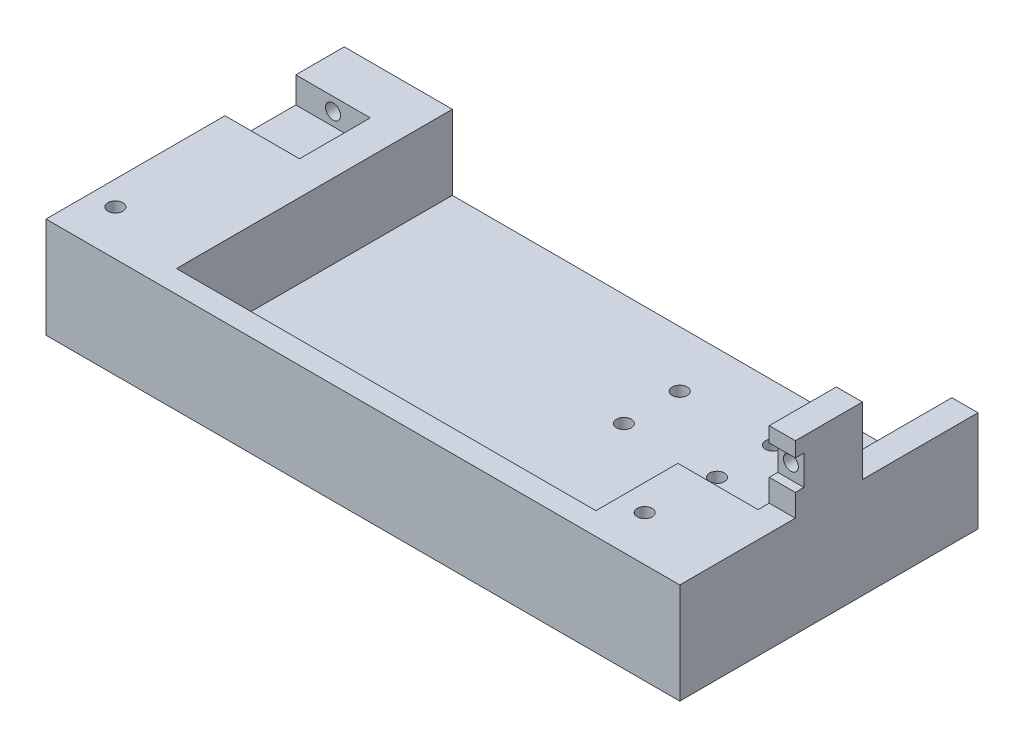
SolidWorks part; units mm, degrees
ref_plane "Front Plane" through (0, 0, 0) normal (0, 0, 1) x (1, 0, 0)
ref_plane "Top Plane" through (0, 0, 0) normal (0, 1, 0) x (1, 0, 0)
ref_plane "Right Plane" through (0, 0, 0) normal (1, 0, 0) x (0, 0, -1)
sketch "Sketch1" plane through (0, 0, 0) normal (0, 1, 0) x (1, 0, 0)
  line L1 (-79.8297, 39.708) -> (90.1703, 39.708)
  line L2 (-79.8297, 39.708) -> (-79.8297, -40.292)
  line L3 (-79.8297, -40.292) -> (90.1703, -40.292)
  line L4 (90.1703, 39.708) -> (90.1703, -40.292)
  dimension "D1" = 170
  dimension "D2" = 80
extrude "Boss-Extrude1" add sketch "Sketch1" along normal blind 7
sketch "Sketch2" plane through (0, 7, 0) normal (0, 1, 0) x (1, 0, 0)
  line L0 (-79.8297, 39.708) -> (-79.8297, -40.292) construction
  line L1 (-79.8297, -40.292) -> (90.1703, -40.292) construction
  line L2 (-79.8297, 8.708) -> (-72.8297, 8.708)
  line L3 (-79.8297, 8.708) -> (-79.8297, -9.292)
  line L4 (-79.8297, -9.292) -> (-72.8297, -9.292)
  line L5 (-72.8297, 8.708) -> (-72.8297, -9.292)
  line L6 (90.1703, 39.708) -> (-79.8297, 39.708) construction
  dimension "D1" = 7
  dimension "D2" = 18
  dimension "D3" = 31
  dimension "D4" = 31
extrude "Boss-Extrude2" add sketch "Sketch2" along normal blind 18
sketch "Sketch3" plane through (0, 0, -8.708) normal (0, 0, -1) x (-1, 0, 0)
  line L0 (79.8297, 25) -> (79.8297, 7) construction
  line L1 (72.8297, 7) -> (79.8297, 7) construction
  circle A0 centre (76.3297, 17) radius 2
  dimension "D1" = 3.5
  dimension "D2" = 10
extrude "Cut-Extrude1" cut sketch "Sketch3" against normal blind 20
sketch "Sketch4" plane through (0, 0, 9.292) normal (0, 0, 1) x (1, 0, 0)
  line L0 (-79.8297, 25) -> (-79.8297, 7) construction
  line L1 (-79.8297, 21) -> (-72.8297, 21)
  line L2 (-79.8297, 21) -> (-79.8297, 13)
  line L3 (-79.8297, 13) -> (-72.8297, 13)
  line L4 (-72.8297, 21) -> (-72.8297, 13)
  line L5 (-72.8297, 25) -> (-72.8297, 7) construction
  line L6 (-79.8297, 7) -> (90.1703, 7) construction
  dimension "D1" = 8
  dimension "D2" = 6
extrude "Cut-Extrude2" cut sketch "Sketch4" against normal blind 2.3
sketch "Sketch6" plane through (0, 7, 0) normal (0, 1, 0) x (1, 0, 0)
  line L1 (90.1703, -40.292) -> (90.1703, 39.708) construction
  line L2 (90.1703, 39.708) -> (-79.8297, 39.708) construction
  line L3 (70.1703, 7.708) -> (90.1703, 7.708)
  line L4 (70.1703, 7.708) -> (70.1703, 26.708)
  line L5 (70.1703, 26.708) -> (90.1703, 26.708)
  line L6 (90.1703, 7.708) -> (90.1703, 26.708)
  dimension "D3" = 20
  dimension "D4" = 13
  dimension "D5" = 19
extrude "Cut-Extrude4" cut sketch "Sketch6" against normal blind 11
sketch "Sketch7" plane through (0, 0, -26.708) normal (0, 0, 1) x (1, 0, 0)
  line L0 (90.1703, 0) -> (90.1703, 7) construction
  line L1 (90.1703, 7) -> (70.1703, 7) construction
  circle A0 centre (80.1703, 3.5) radius 2
  dimension "D1" = 10
  dimension "D2" = 3.5
extrude "Cut-Extrude5" cut sketch "Sketch7" against normal blind 25
extrude "Cut-Extrude6" cut sketch "Sketch7<2>" along normal blind 25
sketch "Sketch7<2>" plane through (0, 0, -26.708) normal (0, 0, 1) x (1, 0, 0) same geometry as "Sketch7"
sketch "Sketch8" plane through (0, 0, 0) normal (0, -1, 0) x (1, 0, 0)
  line L1 (-79.8297, 40.292) -> (90.1703, 40.292)
  line L2 (-79.8297, 40.292) -> (-79.8297, -39.708)
  line L3 (-79.8297, -39.708) -> (90.1703, -39.708)
  line L4 (90.1703, 40.292) -> (90.1703, -39.708)
extrude "Boss-Extrude3" add sketch "Sketch8" along normal blind 20
sketch "Sketch9" plane through (0, 7, 0) normal (0, 1, 0) x (1, 0, 0)
  line L0 (-79.8297, -40.292) -> (90.1703, -40.292) construction
  line L1 (-72.8297, -40.292) -> (61.1703, -40.292)
  line L2 (-72.8297, -40.292) -> (-72.8297, 39.708)
  line L3 (-72.8297, 39.708) -> (61.1703, 39.708)
  line L4 (61.1703, -40.292) -> (61.1703, 39.708)
  line L5 (90.1703, 39.708) -> (-79.8297, 39.708) construction
  line L6 (-72.8297, -9.292) -> (-72.8297, 8.708) construction
  line L7 (70.1703, 26.708) -> (70.1703, 7.708) construction
  dimension "D1" = 0
  dimension "D2" = 9
extrude "Cut-Extrude7" cut sketch "Sketch9" against normal blind 20
sketch "Sketch12" plane through (0, -13, 0) normal (0, 1, 0) x (1, 0, 0)
  line L0 (-72.8297, -9.292) -> (-72.8297, -40.292) construction
  line L1 (-72.8297, -12.292) -> (61.1703, -12.292)
  line L2 (-72.8297, -12.292) -> (-72.8297, -40.292)
  line L3 (-72.8297, -40.292) -> (61.1703, -40.292)
  line L4 (61.1703, -12.292) -> (61.1703, -40.292)
  dimension "D1" = 28
extrude "Boss-Extrude4" add sketch "Sketch12" along normal blind 20
sketch "Sketch10" plane through (0, -20, 0) normal (0, -1, 0) x (1, 0, 0)
  line L1 (90.1703, 40.292) -> (-79.8297, 40.292) construction
  line L2 (-79.8297, 40.292) -> (-79.8297, -39.708) construction
  circle A0 centre (83.6703, 28.192) radius 2
  circle A2 centre (-58.3297, 28.192) radius 2
  dimension "D1" = 21.5
  dimension "D2" = 142
  dimension "D3" = 12.1
  dimension "D4" = 12.1
extrude "Cut-Extrude9" cut sketch "Sketch10" against normal through all both and the other way through all
sketch "Sketch13" plane through (0, 7, 0) normal (0, 1, 0) x (1, 0, 0)
  line L0 (61.1703, -12.292) -> (-72.8297, -12.292) construction
  line L1 (-51.3297, -12.292) -> (61.1703, -12.292)
  line L2 (-51.3297, -12.292) -> (-51.3297, -34.292)
  line L3 (-51.3297, -34.292) -> (61.1703, -34.292)
  line L4 (61.1703, -12.292) -> (61.1703, -34.292)
  line L5 (61.1703, -12.292) -> (61.1703, 39.708) construction
  line L6 (-79.8297, -40.292) -> (90.1703, -40.292) construction
  circle A0 centre (-58.3297, -28.192) radius 2 construction
  dimension "D1" = 0
  dimension "D2" = 6
  dimension "D3" = 7
extrude "Cut-Extrude10" cut sketch "Sketch13" against normal blind 20
sketch "Sketch14" plane through (0, -13, 0) normal (0, 1, 0) x (1, 0, 0)
  line L0 (-79.8297, -40.292) -> (-79.8297, 39.708) construction
  line L1 (-79.8297, 39.708) -> (90.1703, 39.708) construction
  circle A0 centre (-39.8297, 24.708) radius 2
  circle A1 centre (-39.8297, 9.708) radius 2
  circle A2 centre (-14.8297, 9.708) radius 2
  circle A3 centre (-14.8297, 24.708) radius 2
  dimension "D1" = 40
  dimension "D3" = 25
  dimension "D2" = 15
  dimension "D4" = 25
  dimension "D5" = 15
  dimension "D6" = 15
  dimension "D7" = 40
extrude "Cut-Extrude11" cut sketch "Sketch14" against normal blind 10
mirror "Mirror2" about plane through (90.1703, 7, -39.708) normal (-1, 0, 0) of bodies 116
delete or keep bodies "Body-Delete/Keep 1" type delete bodies bodies 116
